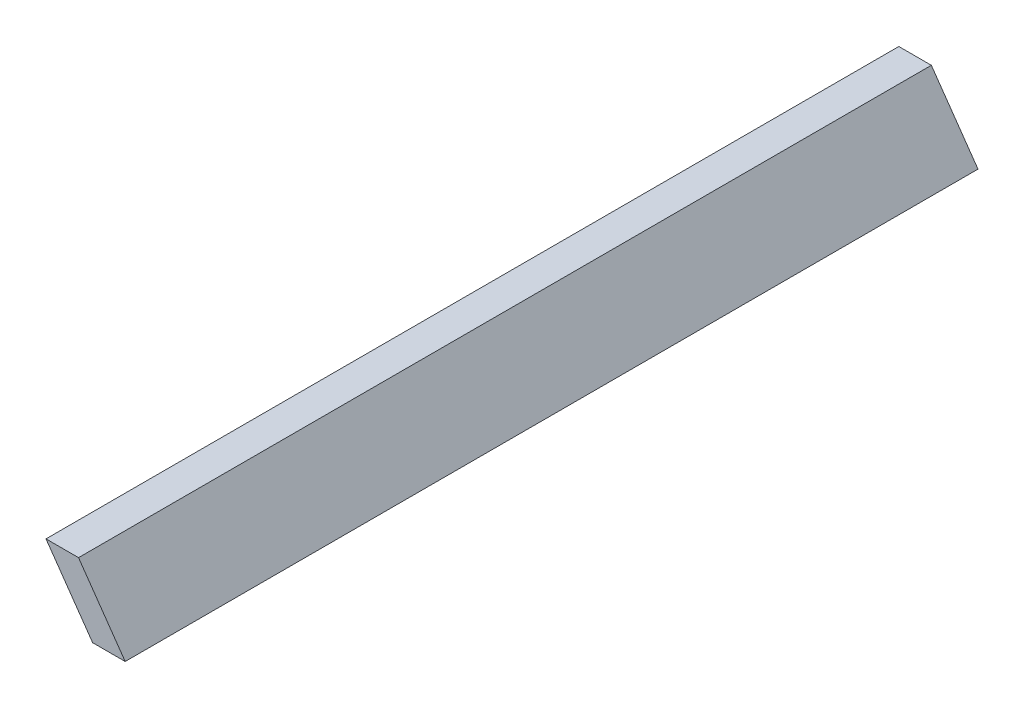
SolidWorks part; units mm, degrees
material "Gray Cast Iron"
ref_plane "Front Plane" through (0, 0, 0) normal (0, 0, 1) x (1, 0, 0)
ref_plane "Top Plane" through (0, 0, 0) normal (0, 1, 0) x (1, 0, 0)
ref_plane "Right Plane" through (0, 0, 0) normal (1, 0, 0) x (0, 0, -1)
sketch "Sketch6" plane through (0, 0, 0) normal (0, 0, 1) x (1, 0, 0)
  line B0 (-34.7427, -15.875) -> (92.2573, -15.875)
  line B1 (92.2573, 0) -> (65.2665, 0)
  line B2 (-11.1158, 15.875) -> (0, 0)
  line B3 (0, 0) -> (-34.7427, 0)
  line B4 (-7.7519, 0) -> (-18.8677, 15.875)
  line B5 (-18.8677, 15.875) -> (-11.1158, 15.875)
  line B6 (12.701, 15.875) -> (12.701, -3.175)
  line B7 (12.701, -3.175) -> (44.8136, -3.175)
  line B8 (12.701, 15.875) -> (-11.1158, 15.875)
  line B9 (-34.7427, 0) -> (-34.7427, 31.75)
  line B10 (-34.7427, 31.75) -> (92.2573, 31.75)
  line B11 (92.2573, 31.75) -> (92.2573, 0)
  line B12 (28.7573, 31.75) -> (28.7573, -15.875) construction
  line B13 (-7.7519, 0) -> (65.2665, 0) construction
  line B14 (0.0553, 21.082) -> (57.4593, 21.082) construction
  line B15 (3.3573, -8.001) -> (54.1573, -8.001) construction
  line B16 (3.3573, -8.001) -> (3.3573, 7.9375) construction
  line B17 (54.1573, -8.001) -> (54.1573, 7.9375) construction
  line B18 (-24.0747, 7.9375) -> (81.5893, 7.9375) construction
  circle B19 centre (28.7573, 6.35) radius 18.669 construction
sketch_block_instance "dovetail pair-1"
sketch_block "dovetail pair" parameters "D8"=37.338, "D1"=55, "D2"=127, "D3"=6.35, "D4"=15.875, "D5"=31.75, "D6"=95.25, "D7"=19.05, "D9"=55, "D10"=31.75, "D11"=50.8, "D12"=23.876, "D13"=7.874, "D14"=10.668, "D15"=34.798, "D16"=21.082, "D17"=7.9375
sketch "end-profile" plane through (0, 0, 0) normal (0, 0, 1) x (1, 0, 0)
  line L0 (0, 0) -> (-7.7519, 0)
  line L4 (-11.1158, 15.875) -> (0, 0) construction
  line L5 (-18.8677, 15.875) -> (-11.1158, 15.875) construction
  line L6 (-7.7519, 0) -> (-18.8677, 15.875) construction
  line L7 (-11.1158, 15.875) -> (0, 0)
  line L8 (-18.8677, 15.875) -> (-11.1158, 15.875)
  line L9 (-7.7519, 0) -> (-18.8677, 15.875)
extrude "Boss-Extrude1" add sketch "end-profile" along normal blind 203.2
ref_plane "screw pocket Plane1" through (-18.8677, 0, 0) normal (1, 0, 0) x (0, 0, -1)
sketch "Sketch4" plane through (-18.8677, 0, 0) normal (1, 0, 0) x (0, 0, -1)
  line L0 (0, 7.9375) -> (-203.2, 7.9375) construction
  line L1 (-203.2, 15.875) -> (-203.2, 0) construction
  line L3 (-181.1871, 7.9375) -> (-181.1871, 0)
  line L4 (-181.1871, 0) -> (-174.4129, 0)
  line L5 (-174.4129, 0) -> (-174.4129, 7.9375)
  line L6 (-143.0871, 7.9375) -> (-143.0871, 0)
  line L7 (-143.0871, 0) -> (-136.3129, 0)
  line L8 (-136.3129, 0) -> (-136.3129, 7.9375)
  line L9 (-104.9871, 7.9375) -> (-104.9871, 0)
  line L10 (-104.9871, 0) -> (-98.2129, 0)
  line L11 (-98.2129, 0) -> (-98.2129, 7.9375)
  line L12 (-66.8871, 7.9375) -> (-66.8871, 0)
  line L13 (-66.8871, 0) -> (-60.1129, 0)
  line L14 (-60.1129, 0) -> (-60.1129, 7.9375)
  line L15 (-28.7871, 7.9375) -> (-28.7871, 0)
  line L16 (-28.7871, 0) -> (-22.0129, 0)
  line L17 (-22.0129, 0) -> (-22.0129, 7.9375)
  line L18 (-181.1871, 7.9375) -> (-143.0871, 7.9375) construction
  line L19 (-203.2, 0) -> (0, 0) construction
  line L21 (0, 0) -> (0, 15.875) construction
  arc A0 (-174.4129, 7.9375) -> (-181.1871, 7.9375) centre (-177.8, 7.9375) ccw
  arc A1 (-136.3129, 7.9375) -> (-143.0871, 7.9375) centre (-139.7, 7.9375) ccw
  arc A2 (-98.2129, 7.9375) -> (-104.9871, 7.9375) centre (-101.6, 7.9375) ccw
  arc A3 (-60.1129, 7.9375) -> (-66.8871, 7.9375) centre (-63.5, 7.9375) ccw
  arc A4 (-22.0129, 7.9375) -> (-28.7871, 7.9375) centre (-25.4, 7.9375) ccw
  dimension "D1" = 6.7742
  dimension "D2" = 38.1
  dimension "D3" = 5
extrude "Cut-Extrude1" cut sketch "Sketch4" along normal blind 7.112
sketch "Sketch5" [suppressed] plane through (-18.8677, 0, 0) normal (1, 0, 0) x (0, 0, -1)
  line L0 (0, 7.9375) -> (-127, 7.9375) construction
  line L3 (-104.9871, 7.9375) -> (-104.9871, 0)
  line L5 (-104.9871, 0) -> (-98.2129, 0)
  line L6 (-98.2129, 0) -> (-98.2129, 7.9375)
  line L7 (-66.8871, 7.9375) -> (-66.8871, 0)
  line L8 (-66.8871, 0) -> (-60.1129, 0)
  line L9 (-60.1129, 0) -> (-60.1129, 7.9375)
  line L10 (-28.7871, 7.9375) -> (-28.7871, 0)
  line L11 (-28.7871, 0) -> (-22.0129, 0)
  line L12 (-22.0129, 0) -> (-22.0129, 7.9375)
  line L13 (-104.9871, 7.9375) -> (-66.8871, 7.9375) construction
  line L14 (-127, 0) -> (-127, 15.875) construction
  line L15 (-127, 0) -> (0, 0) construction
  line L16 (0, 0) -> (0, 15.875) construction
  arc A0 (-98.2129, 7.9375) -> (-104.9871, 7.9375) centre (-101.6, 7.9375) ccw
  arc A1 (-60.1129, 7.9375) -> (-66.8871, 7.9375) centre (-63.5, 7.9375) ccw
  arc A2 (-22.0129, 7.9375) -> (-28.7871, 7.9375) centre (-25.4, 7.9375) ccw
  dimension "D1" = 6.7742
  dimension "D2" = 38.1
extrude "Cut-Extrude2" [suppressed] cut sketch "Sketch5" along normal blind 7.112
equation "\"dovetail-angle\" = 55"
equation "\"dovetail-stock-width\" = 5"
equation "\"dovetail-stock-height\" = 1.25"
equation "\"dovetail-depth\" = 0.5 * \"dovetail-stock-height\""
equation "\"dovetail-throat-width\" = \"dovetail-stock-width\" - (2 * \"dovetail-depth\")"
equation "\"delta-x\" = 6"
equation "\"delta-y\" = 3"
equation "\"delta-z\"= 2.5"
equation "\"acme-nut-height\"= 0.5"
equation "\"acme-nut-width\"= 0.75"
equation "\"gib-thickness\" = 0.25"
equation "\"x-slide-length\" = \"dovetail-stock-width\" + \"delta-x\""
equation "\"y-slide-length\" = \"dovetail-stock-width\" + \"delta-y\""
equation "\"dog-point-diam\" = .149"
equation "\"dog-point-length\" = .067"
equation "\"dovetail-double-height\" = 2 * \"dovetail-depth\" + 0.5"
equation "\"acme-major-diam\" = .5"
equation "\"acme-pitch-diam\" = 0.45"
equation "\"acme-minor-diam\" = 0.4"
equation "\"acme-nut-od\" = 1.47"
equation "\"acme-nut-length\" = 1"
equation "\"acme-nut-trim-height\" = .75"
equation "\"screw-bearing-od\" = 0.5"
equation "\"screw-bearing-length\" = .375"
equation "\"screw-bearing-id\" = .375"
equation "\"end-plate-thickness\" = \"screw-bearing-length\""
equation "\"screw-add-length\" = 2 * \"end-plate-thickness\" + 1 + 0.5"
equation "\"x-screw-length\" = \"x-slide-length\" + \"screw-add-length\""
equation "\"y-screw-length\" = \"y-slide-length\" + \"screw-add-length\""
equation "\"acme-nut-mount-hole-space-horz\" = 0.95"
equation "\"acme-nut-mount-hole-space-vert\" = 0.5 * \"acme-nut-length\""
equation "\"vise-hole-center-dist\" = 6.75"
equation "\"wiper_plate_clearance\" = .03"
equation "\"dial-width\" = 0.5"
equation "\"quarter-twenty-free-fit\" = .2667"
equation "\"D1@Sketch4\"=\"quarter-twenty-free-fit\""
equation "\"D1@Sketch5\"=\"quarter-twenty-free-fit\""
equation "\"D2@dovetail pair\"=\"dovetail-stock-width\""
equation "\"D1@dovetail pair\"=\"dovetail-angle\""
equation "\"D3@dovetail pair\"=\"gib-thickness\""
equation "\"D4@dovetail pair\"=\"dovetail-depth\""
equation "\"D5@dovetail pair\"=\"dovetail-stock-height\""
equation "\"D6@dovetail pair\"=\"dovetail-throat-width\""
equation "\"D10@dovetail pair\"=\"dovetail-stock-height\""
equation "\"D7@dovetail pair\"=\"acme-nut-trim-height\""
equation "\"D8@dovetail pair\"=\"acme-nut-od\""
equation "\"D9@dovetail pair\"=\"dovetail-angle\""
equation "\"D17@dovetail pair\"=\"dovetail-depth\"/2"
equation "\"acme-nut-trim-width\" = 1.25"
equation "\"acme_nut_clearance\" = .01"
equation "\"dovetail_male_clearance\" = .01"
